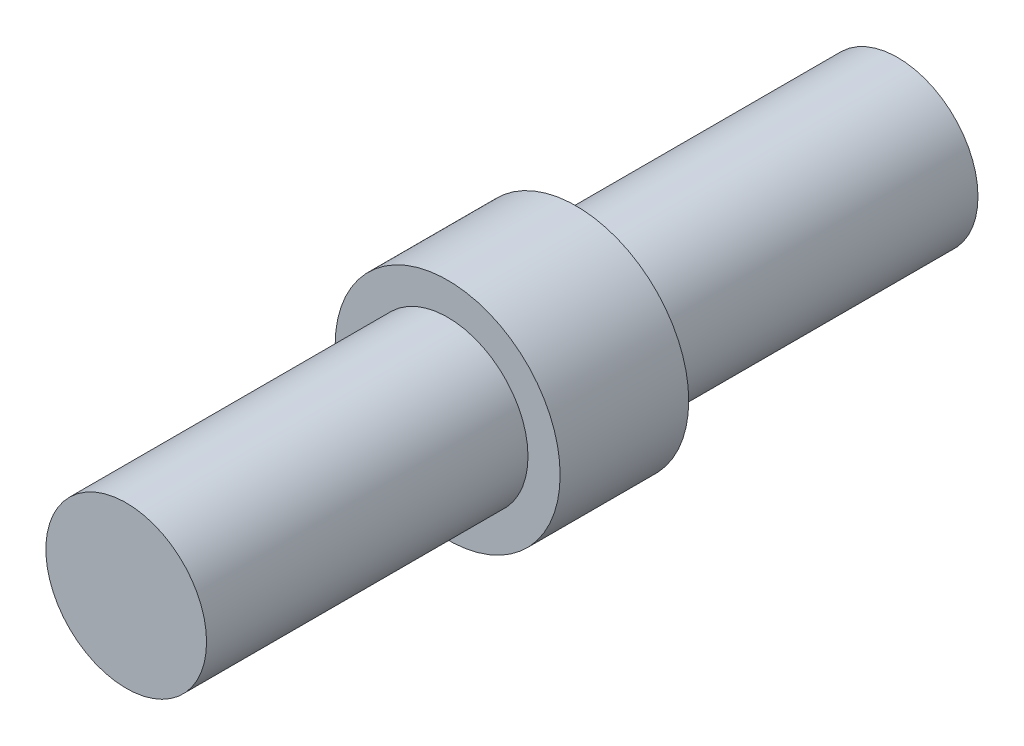
SolidWorks part; units mm, degrees
ref_plane "Front Plane" through (0, 0, 0) normal (0, 0, 1) x (1, 0, 0)
ref_plane "Top Plane" through (0, 0, 0) normal (0, 1, 0) x (1, 0, 0)
ref_plane "Right Plane" through (0, 0, 0) normal (1, 0, 0) x (0, 0, -1)
sketch "Sketch1" plane through (0, 0, 0) normal (0, 0, 1) x (1, 0, 0)
  circle A0 centre (0, 0) radius 2.5
  dimension "D1" = 5
extrude "Boss-Extrude1" add sketch "Sketch1" along normal blind 10
sketch "Sketch2" plane through (0, 0, 10) normal (0, 0, 1) x (1, 0, 0)
  circle A0 centre (0, 0) radius 3.5
  dimension "D1" = 7
extrude "Boss-Extrude2" add sketch "Sketch2" along normal blind 4
extrude "Boss-Extrude3" add sketch "Sketch1<2>" along normal blind 10 from surface starting at face at (3.5, 0, 14)
sketch "Sketch1<2>" plane through (0, 0, 0) normal (0, 0, 1) x (1, 0, 0) same geometry as "Sketch1"
